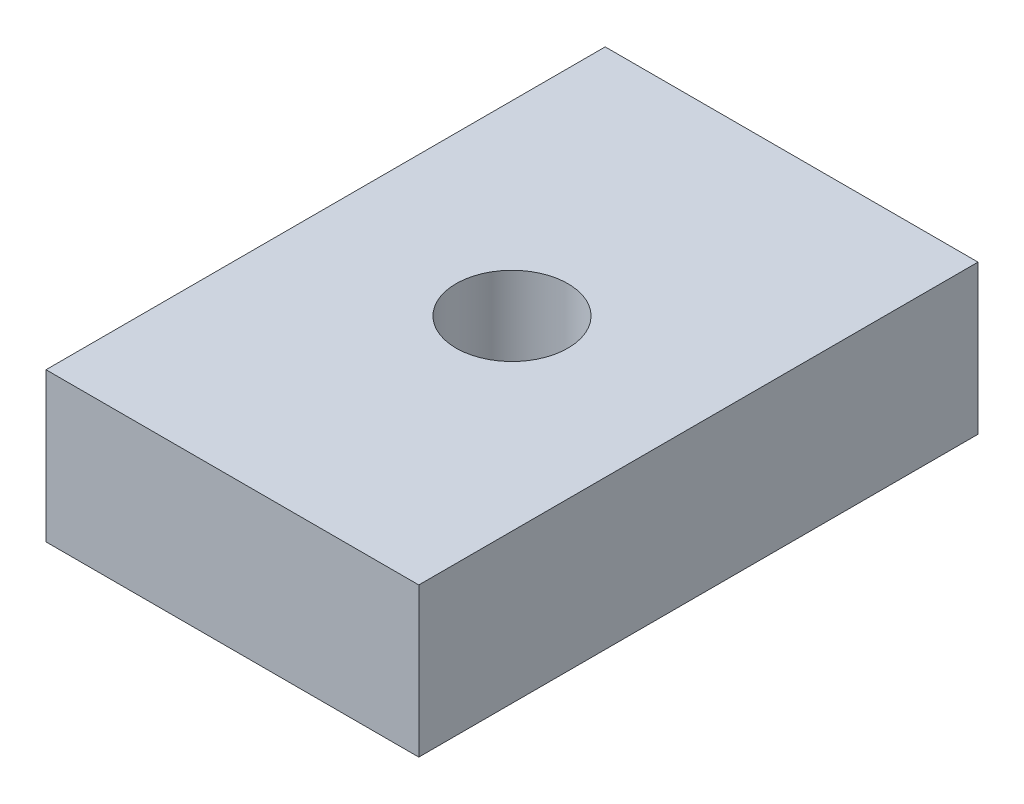
SolidWorks part; units mm, degrees
ref_plane "Front Plane" through (0, 0, 0) normal (0, 0, 1) x (1, 0, 0)
ref_plane "Top Plane" through (0, 0, 0) normal (0, 1, 0) x (1, 0, 0)
ref_plane "Right Plane" through (0, 0, 0) normal (1, 0, 0) x (0, 0, -1)
sketch "Sketch2" plane through (0, 0, 0) normal (1, 0, 0) x (0, 0, -1)
  line L0 (0, 0) -> (15, 0)
  line L4 (15, 4) -> (0, 4)
  line L7 (0, 4) -> (0, 0)
  line L8 (15, 0) -> (15, 4)
  dimension "D2" = 4
  dimension "D3" = 15
extrude "ProfileBoss-Extrude1" add sketch "Sketch2" along normal blind 10
sketch "MountHolesSketch5" plane through (0, 4, 0) normal (0, 1, 0) x (1, 0, 0)
  line L0 (0, 15) -> (0, 0) construction
  line L3 (10, 0) -> (0, 0) construction
  circle A0 centre (5, 7.5) radius 1.5
  dimension "D1" = 3
  dimension "D2" = 5
  dimension "D4" = 7.5
extrude "MountHolesCut-Extrude2" cut sketch "MountHolesSketch5" against normal through all
equation "\"ChannelRiserHeight\"= 4mm"
equation "\"D2@Sketch2\"=\"ChannelRiserHeight\""
equation "\"ChannelWidth\"= 15mm"
equation "\"ChannelLength\"= 10mm"
equation "\"D1@ProfileBoss-Extrude1\"=\"ChannelLength\""
equation "\"D3@Sketch2\"=\"ChannelWidth\""
equation "\"D4@MountHolesSketch5\"=\"ChannelWidth\"/2"
equation "\"D2@MountHolesSketch5\"=\"ChannelLength\"/2"
